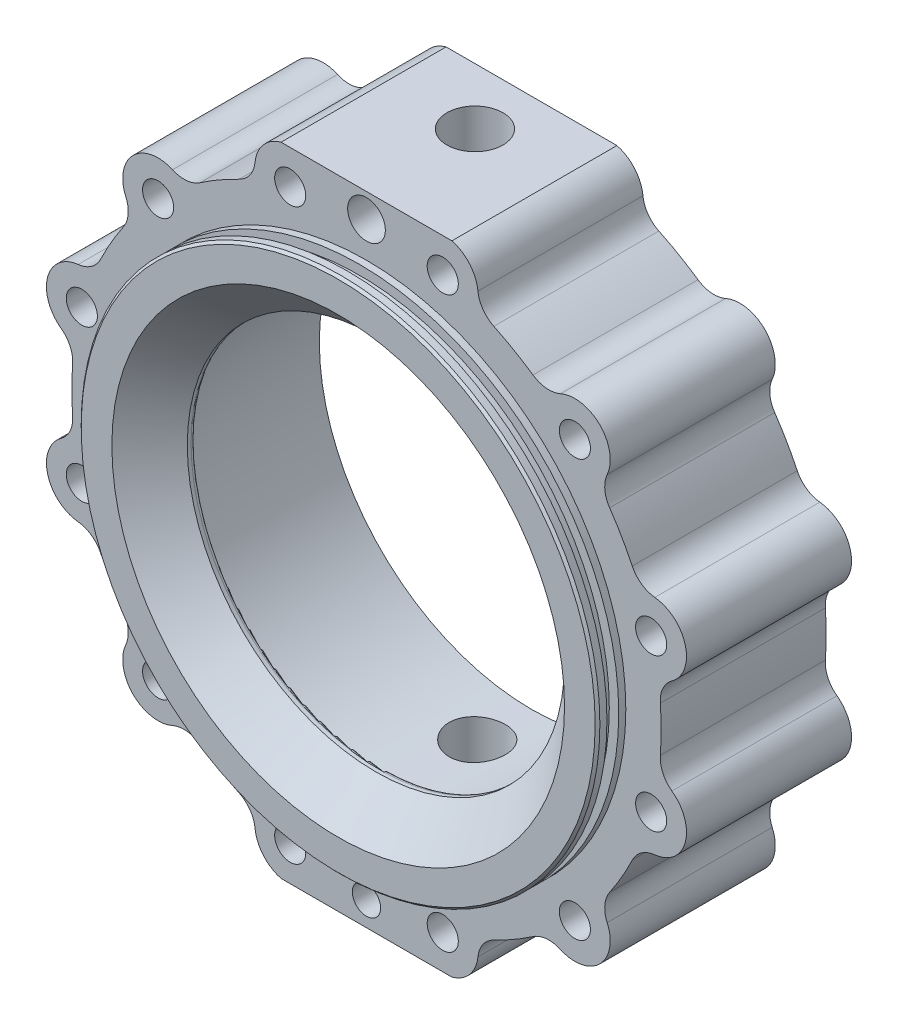
SolidWorks part; units mm, degrees
ref_plane "Front Plane" through (0, 0, 0) normal (0, 0, 1) x (1, 0, 0)
ref_plane "Top Plane" through (0, 0, 0) normal (0, 1, 0) x (1, 0, 0)
ref_plane "Right Plane" through (0, 0, 0) normal (1, 0, 0) x (0, 0, -1)
sketch "Sketch1" plane through (0, 0, 0) normal (0, 1, 0) x (1, 0, 0)
  line L0 (-55, -15.7958) -> (-55, -9.7958)
  line L2 (-55, -9.7958) -> (-70, -9.7958)
  line L3 (-55, -15.7958) -> (-40, -15.7958)
  line L4 (-40, -15.7958) -> (-40, -6)
  line L5 (-40, -6) -> (-45, -6)
  line L6 (-45, -6) -> (-45, 25.2042)
  line L7 (-45, 25.2042) -> (-70, 25.2042)
  line L8 (-70, 25.2042) -> (-70, -9.7958)
  line L12 (0, 52.7074) -> (0, -119.6493) construction
  dimension "D1" = 80
  dimension "D2" = 31.2042
  dimension "D3" = 140
  dimension "D4" = 90
  dimension "D5" = 110
  dimension "D6" = 6
revolve "Revolve1" add sketch "Sketch1" angle 360 about L12
sketch "Sketch2" plane through (0, 0, 9.7958) normal (0, 0, 1) x (1, 0, 0)
  line L0 (0, 62.5) -> (0, -62.5) construction
  circle A0 centre (0, 0) radius 62.5 construction
  circle A2 centre (0, -62.5) radius 3
  dimension "D1" = 125
  dimension "D3" = 6
extrude "Cut-Extrude1" cut sketch "Sketch2" against normal blind 9 contours A2
sketch "Sketch3" plane through (0, 0, 9.7958) normal (0, 0, 1) x (1, 0, 0)
  line L0 (0, 0) -> (0, 62.5) construction
  circle A0 centre (0, 62.5) radius 4
  dimension "D2" = 8
  dimension "D1" = 62.5
extrude "Cut-Extrude2" cut sketch "Sketch3" against normal blind 10
sketch "Bolt Holes" plane through (0, 0, 9.7958) normal (0, 0, 1) x (1, 0, 0)
  line L2 (-44.1942, 44.1942) -> (0, 0) construction
  line L3 (0, 0) -> (0, 62.5) construction
  circle A1 centre (0, 0) radius 62.5 construction
  point P0 (-60.3704, 16.1762)
  point P5 (-44.1942, 44.1942)
  point P8 (-16.1762, 60.3704)
  point P11 (16.1762, 60.3704)
  point P15 (44.1942, 44.1942)
  point P16 (60.3704, 16.1762)
  point P17 (60.3704, -16.1762)
  point P18 (44.1942, -44.1942)
  point P19 (16.1762, -60.3704)
  point P20 (-16.1762, -60.3704)
  point P21 (-44.1942, -44.1942)
  point P22 (-60.3704, -16.1762)
  point P23 (0, 0)
  point P30 (-44.1942, 44.1942)
  point P37 (44.1942, -44.1942)
  dimension "D3" = 45
  dimension "D2" = 125
  dimension "D1" = 12
sketch "Sketch9" plane through (0, 0, 0) normal (0, 1, 0) x (1, 0, 0)
  line L0 (-55, -9.7958) -> (-55, -15.7958) construction
  line L1 (-55, -13.7958) -> (-53, -13.7958)
  line L2 (-55, -13.7958) -> (-55, -11.2958)
  line L3 (-55, -11.2958) -> (-53, -11.2958)
  line L4 (-53, -13.7958) -> (-53, -11.2958)
  line L6 (0, 11.3077) -> (0, -18.9957) construction
  dimension "D1" = 2
  dimension "50" = 53
  dimension "D2" = 2.5
revolve "Oring groove" cut sketch "Sketch9" angle 360 about L6
chamfer "Chamfer1" distance 0.5 angle 45 1 edges at (-55, 0, 15.7958)
hole_wizard "M6 Clearance Hole1" positions "Bolt Holes" profile "Sketch10" hole size "M6" standard "ANSI Metric" end condition through all
sketch "Sketch10" plane through (-60.3704, 16.1762, 9.7958) normal (1, 0, 0) x (0, -1, 0)
  line L0 (0, 0) -> (0, 35)
  line L1 (0, 35) -> (3.3, 35)
  line L2 (3.3, 35) -> (3.3, 0)
  line L5 (3.3, 0) -> (0, 0)
  line L11 (0, -6.35) -> (0, 107.95) construction
  dimension "Thru Hole Dia." = 6.6
  dimension "Thru Hole Depth" = 35
fillet "Fillet2" radius 1 1 edges at (-40, 0, 6)
chamfer "Chamfer2" distance 8 angle 45 1 edges at (-40, 0, 15.7958)
sketch "Sketch11" plane through (0, 0, -25.2042) normal (0, 0, -1) x (-1, 0, 0)
  line L0 (-18.1173, 67.6148) -> (18.1173, 67.6148)
  line L1 (-18.1173, -67.6148) -> (18.1173, -67.6148)
  arc A0 (-64.7749, -10.1058) -> (-61.1496, -23.6356) centre (-60.3704, -16.1762) ccw
  arc A1 (-56.3622, -27.0102) -> (-61.1496, -23.6356) centre (-61.773, -29.6031) ccw
  arc A2 (-56.3622, -27.0102) -> (-51.5726, -35.3061) centre (0, 0) ccw
  arc A3 (-51.0438, -41.1393) -> (-51.5726, -35.3061) centre (-56.5236, -38.6954) ccw
  arc A4 (-51.0438, -41.1393) -> (-41.1393, -51.0438) centre (-44.1942, -44.1942) ccw
  arc A5 (-35.3061, -51.5726) -> (-41.1393, -51.0438) centre (-38.6954, -56.5236) ccw
  arc A6 (-35.3061, -51.5726) -> (-27.0102, -56.3622) centre (0, 0) ccw
  arc A7 (-23.6356, -61.1496) -> (-27.0102, -56.3622) centre (-29.6031, -61.773) ccw
  arc A8 (-23.6356, -61.1496) -> (-18.1173, -67.6148) centre (-16.1762, -60.3704) ccw
  arc A10 (18.1173, -67.6148) -> (23.6356, -61.1496) centre (16.1762, -60.3704) ccw
  arc A11 (27.0102, -56.3622) -> (23.6356, -61.1496) centre (29.6031, -61.773) ccw
  arc A12 (27.0102, -56.3622) -> (35.3061, -51.5726) centre (0, 0) ccw
  arc A13 (41.1393, -51.0438) -> (35.3061, -51.5726) centre (38.6954, -56.5236) ccw
  arc A14 (41.1393, -51.0438) -> (51.0438, -41.1393) centre (44.1942, -44.1942) ccw
  arc A15 (51.5726, -35.3061) -> (51.0438, -41.1393) centre (56.5236, -38.6954) ccw
  arc A16 (51.5726, -35.3061) -> (56.3622, -27.0102) centre (0, 0) ccw
  arc A17 (61.1496, -23.6356) -> (56.3622, -27.0102) centre (61.773, -29.6031) ccw
  arc A18 (61.1496, -23.6356) -> (64.7749, -10.1058) centre (60.3704, -16.1762) ccw
  arc A19 (62.3162, -4.7896) -> (64.7749, -10.1058) centre (68.2986, -5.2494) ccw
  arc A20 (62.3162, -4.7896) -> (62.3162, 4.7896) centre (0, 0) ccw
  arc A21 (64.7749, 10.1058) -> (62.3162, 4.7896) centre (68.2986, 5.2494) ccw
  arc A22 (64.7749, 10.1058) -> (61.1496, 23.6356) centre (60.3704, 16.1762) ccw
  arc A23 (56.3622, 27.0102) -> (61.1496, 23.6356) centre (61.773, 29.6031) ccw
  arc A24 (56.3622, 27.0102) -> (51.5726, 35.3061) centre (0, 0) ccw
  arc A25 (51.0438, 41.1393) -> (51.5726, 35.3061) centre (56.5236, 38.6954) ccw
  arc A26 (51.0438, 41.1393) -> (41.1393, 51.0438) centre (44.1942, 44.1942) ccw
  arc A27 (35.3061, 51.5726) -> (41.1393, 51.0438) centre (38.6954, 56.5236) ccw
  arc A28 (35.3061, 51.5726) -> (27.0102, 56.3622) centre (0, 0) ccw
  arc A29 (23.6356, 61.1496) -> (27.0102, 56.3622) centre (29.6031, 61.773) ccw
  arc A30 (23.6356, 61.1496) -> (18.1173, 67.6148) centre (16.1762, 60.3704) ccw
  arc A32 (-18.1173, 67.6148) -> (-23.6356, 61.1496) centre (-16.1762, 60.3704) ccw
  arc A33 (-27.0102, 56.3622) -> (-23.6356, 61.1496) centre (-29.6031, 61.773) ccw
  arc A34 (-27.0102, 56.3622) -> (-35.3061, 51.5726) centre (0, 0) ccw
  arc A35 (-41.1393, 51.0438) -> (-35.3061, 51.5726) centre (-38.6954, 56.5236) ccw
  arc A36 (-41.1393, 51.0438) -> (-51.0438, 41.1393) centre (-44.1942, 44.1942) ccw
  arc A37 (-51.5726, 35.3061) -> (-51.0438, 41.1393) centre (-56.5236, 38.6954) ccw
  arc A38 (-51.5726, 35.3061) -> (-56.3622, 27.0102) centre (0, 0) ccw
  arc A39 (-61.1496, 23.6356) -> (-56.3622, 27.0102) centre (-61.773, 29.6031) ccw
  arc A40 (-61.1496, 23.6356) -> (-64.7749, 10.1058) centre (-60.3704, 16.1762) ccw
  arc A41 (-62.3162, 4.7896) -> (-64.7749, 10.1058) centre (-68.2986, 5.2494) ccw
  arc A42 (-62.3162, 4.7896) -> (-62.3162, -4.7896) centre (0, 0) ccw
  arc A43 (-64.7749, -10.1058) -> (-62.3162, -4.7896) centre (-68.2986, -5.2494) ccw
  circle A44 centre (0, 0) radius 70 construction
  arc A45 (-18.1173, 67.6148) -> (-18.1173, -67.6148) centre (0, 0) ccw
  arc A46 (18.1173, -67.6148) -> (18.1173, 67.6148) centre (0, 0) ccw
  circle A47 centre (16.1762, -60.3704) radius 3.3 construction
  circle A48 centre (-44.1942, -44.1942) radius 3.3 construction
  circle A49 centre (-60.3704, -16.1762) radius 3.3 construction
  circle A50 centre (-60.3704, 16.1762) radius 3.3 construction
  point P20 (0, 0)
  point P86 (-61.9835, 23.6238)
  circle M57 centre (0, 0) radius 70
  dimension "D1" = 7.5
  dimension "D2" = 6
extrude "looksmaxxing" cut sketch "Sketch11" against normal through all contours A30 A29 A28 A27 A26 M57 | A26 A25 A24 A23 A22 M57 | A22 A21 A20 A19 A18 M57 | A18 A17 A16 A15 A14 M57 | A14 A13 A12 A11 A10 M57 | A8 A7 A6 A5 A4 M57 | A4 A3 A2 A1 A0 M57 | A0 A43 A42 A41 A40 M57 | A40 A39 A38 A37 A36 M57 | A36 A35 A34 A33 A32 M57 | L0 M57 | L1 M57 region at (0, 68.5703, -25.2042) region at (33.2057, 57.514, -25.2042) region at (-33.2057, 57.514, -25.2042) region at (57.514, 33.2057, -25.2042) region at (-57.514, 33.2057, -25.2042) region at (66.4115, 0, -25.2042) region at (-66.4115, 0, -25.2042) region at (57.514, -33.2057, -25.2042) region at (33.2057, -57.514, -25.2042) region at (-57.514, -33.2057, -25.2042) region at (0, -68.5703, -25.2042) region at (-33.2057, -57.514, -25.2042)
hole_wizard "1/4-18 NPSM Tapped Hole1" positions "Sketch13" profile "Sketch14" tap size "1/4-18 NPSM" standard "ANSI Inch"
sketch "Sketch13" plane through (0, 67.6148, 0) normal (0, 1, 0) x (1, 0, 0)
  line L0 (0, 0) -> (0, 25.2042) construction
  line L1 (18.1173, 25.2042) -> (-18.1173, 25.2042) construction
  point P8 (0, 13.2042)
  point P11 (0, 0)
  point P12 (0, 15.2042)
  dimension "D1" = 12
sketch "Sketch14" plane through (0, 67.6148, -13.2042) normal (1, 0, 0) x (0, 0, 1)
  line L0 (0, 0) -> (0, 34.5313)
  line L1 (0, 34.5313) -> (5.9436, 30.96)
  line L2 (5.9436, 30.96) -> (5.9436, 0)
  line L5 (5.9436, 0) -> (0, 0)
  line L10 (0, 34.5313) -> (-5.9436, 30.96) construction
  line L11 (0, -6.35) -> (0, 107.95) construction
  dimension "Tap Drill Dia." = 11.8872
  dimension "Tap Drill Depth" = 30.96
  dimension "Drill Angle" = 118
cosmetic thread "Hole Thread1" parameters "D1"=26.72, "D2"=13.3604
hole_wizard "1/4-18 NPSM Tapped Hole2" positions "Sketch15" profile "Sketch16" tap size "1/4-18 NPSM" standard "ANSI Inch"
sketch "Sketch15" plane through (0, -67.6148, 0) normal (0, -1, 0) x (1, 0, 0)
  line L0 (18.1173, -25.2042) -> (-18.1173, -25.2042) construction
  point P0 (0, -13.7042)
  point P5 (0, 0)
  dimension "D1" = 11.5
sketch "Sketch16" plane through (0, -67.6148, -13.7042) normal (1, 0, 0) x (0, 0, -1)
  line L0 (0, 0) -> (0, 34.5313)
  line L1 (0, 34.5313) -> (5.9436, 30.96)
  line L2 (5.9436, 30.96) -> (5.9436, 0)
  line L5 (5.9436, 0) -> (0, 0)
  line L10 (0, 34.5313) -> (-5.9436, 30.96) construction
  line L11 (0, -6.35) -> (0, 107.95) construction
  dimension "Tap Drill Dia." = 11.8872
  dimension "Tap Drill Depth" = 30.96
  dimension "Drill Angle" = 118
cosmetic thread "Hole Thread2" parameters "D1"=26.72, "D2"=13.3604
